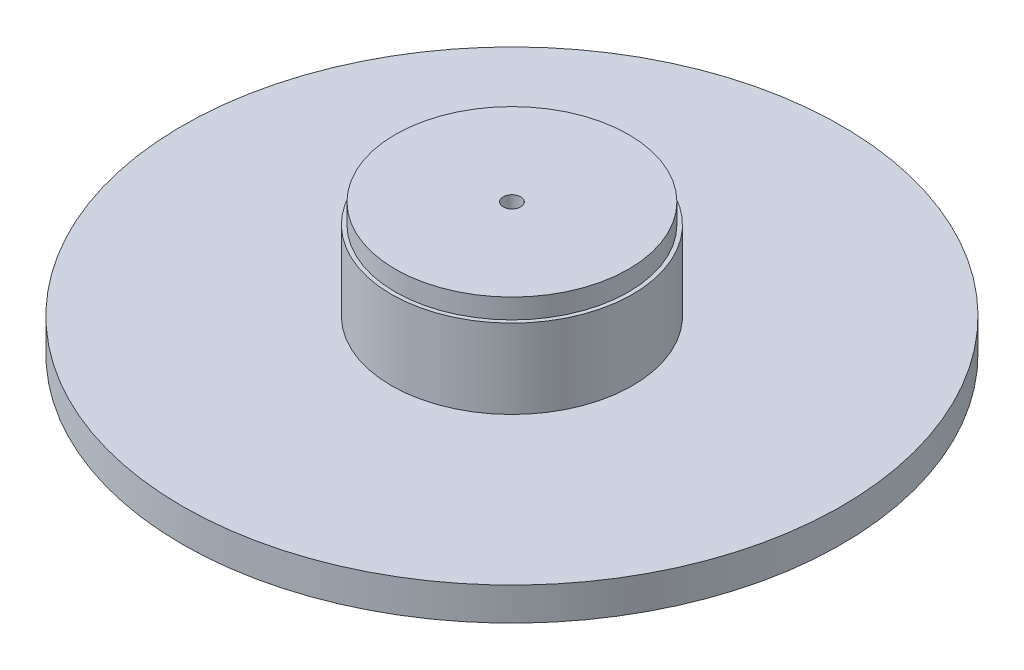
SolidWorks part; units mm, degrees
ref_plane "Front Plane" through (0, 0, 0) normal (0, 0, 1) x (1, 0, 0)
ref_plane "Top Plane" through (0, 0, 0) normal (0, 1, 0) x (1, 0, 0)
ref_plane "Right Plane" through (0, 0, 0) normal (1, 0, 0) x (0, 0, -1)
sketch "Sketch1" plane through (0, 0, 0) normal (0, 1, 0) x (1, 0, 0)
  circle A0 centre (0, 0) radius 44.958
  circle A1 centre (0, 0) radius 46.482
  circle A2 centre (0, 0) radius 127
extrude "Boss-Extrude4" add sketch "Sketch1" along normal blind 12.7 contours A2 A1 region at (-123.4079, 0, 0)
extrude "Boss-Extrude5" add sketch "Sketch1<6>" along normal blind 43.18 contours A1 A0 region at (-45.1673, 0, 0)
sketch "Sketch1<6>" plane through (0, 0, 0) normal (0, 1, 0) x (1, 0, 0) same geometry as "Sketch1"
extrude "Boss-Extrude6" add sketch "Sketch1<7>" along normal blind 50.8 contours A0 region at (0, 0, 0)
sketch "Sketch1<7>" plane through (0, 0, 0) normal (0, 1, 0) x (1, 0, 0) same geometry as "Sketch1"
hole_wizard "CSK for 1/4 Flat Head Machine Screw (100)1" positions "Sketch4" profile "Sketch5" countersink size "1/4" standard "ANSI Inch" end condition through all
sketch "Sketch4" plane through (0, 0, 0) normal (0, -1, 0) x (-1, 0, 0)
  point P0 (0, 0)
sketch "Sketch5" plane through (0, 0, 0) normal (1, 0, 0) x (0, 0, -1)
  line L0 (0, 0) -> (0, 50.8)
  line L1 (0, 50.8) -> (3.3782, 50.8)
  line L2 (3.3782, 50.8) -> (3.3782, 2.5682)
  line L3 (3.3782, 2.5682) -> (6.4389, 0)
  line L5 (6.4389, 0) -> (0, 0)
  line L6 (-3.3782, 2.5682) -> (-6.4389, 0) construction
  line L11 (0, -6.35) -> (0, 107.95) construction
  dimension "Thru Hole Dia." = 6.7564
  dimension "Thru Hole Depth" = 50.8
  dimension "Near C'Sink Dia." = 12.8778
  dimension "Near C'Sink Angle" = 100
